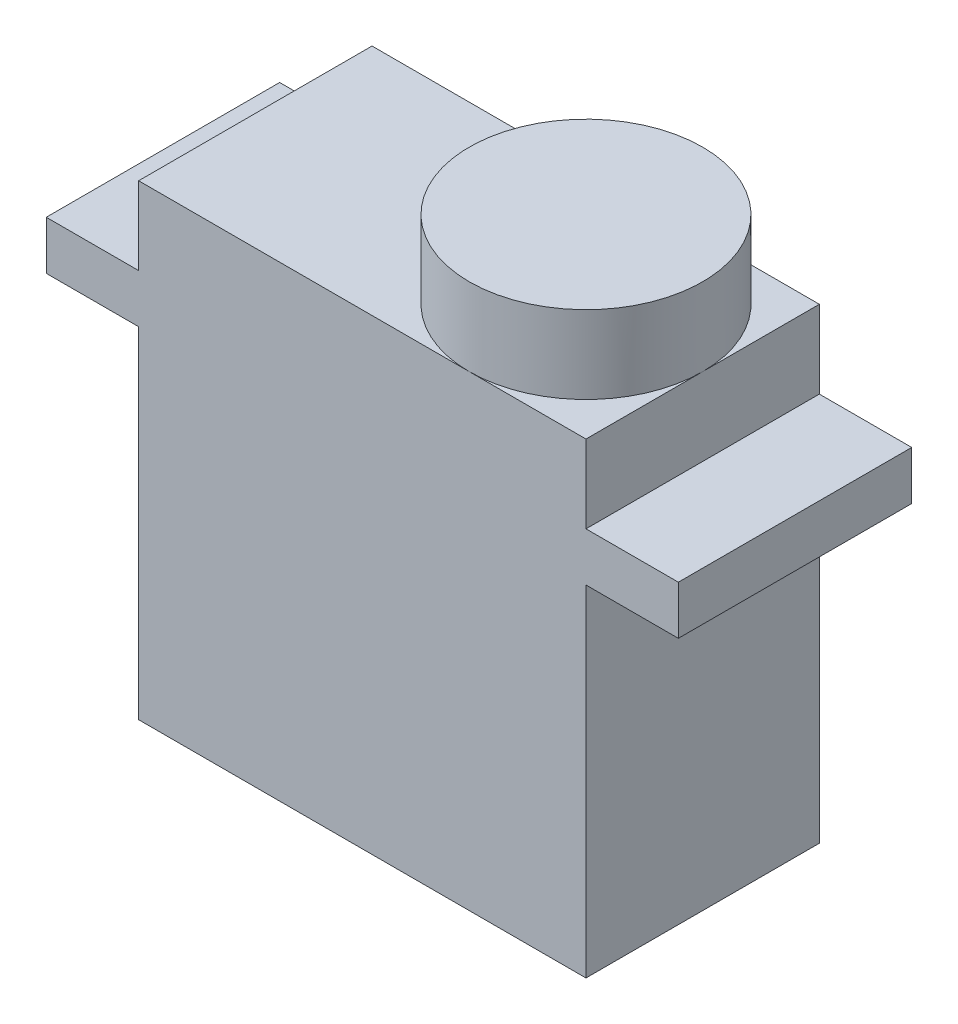
SolidWorks part; units mm, degrees
note: The reader was unsure of these and kept them because the rebuilt part matched: shared geometry of "Sketch1<3>", "Sketch1<4>".
ref_plane "Front Plane" through (0, 0, 0) normal (0, 0, 1) x (1, 0, 0)
ref_plane "Top Plane" through (0, 0, 0) normal (0, 1, 0) x (1, 0, 0)
ref_plane "Right Plane" through (0, 0, 0) normal (1, 0, 0) x (0, 0, -1)
sketch "Sketch1" plane through (0, 0, 0) normal (0, 1, 0) x (1, 0, 0)
  line L1 (-11.5, -6) -> (11.5, -6)
  line L2 (-11.5, -6) -> (-11.5, 6)
  line L3 (-11.5, 6) -> (11.5, 6)
  line L4 (11.5, -6) -> (11.5, 6)
  line L5 (-11.5, -6) -> (11.5, 6) construction
  line L6 (-11.5, 6) -> (11.5, -6) construction
  line L7 (-16.25, -6) -> (16.25, -6)
  line L8 (-16.25, -6) -> (-16.25, 6)
  line L9 (-16.25, 6) -> (16.25, 6)
  line L10 (16.25, -6) -> (16.25, 6)
  line L11 (-16.25, -6) -> (16.25, 6) construction
  line L12 (-16.25, 6) -> (16.25, -6) construction
  circle A0 centre (5.5, 0) radius 6
  point P0 (0, 0)
  point P6 (0, 0)
  dimension "D1" = 23
  dimension "D2" = 12
  dimension "D3" = 32.5
extrude "Boss-Extrude1" add sketch "Sketch1" along normal blind 24 contours A0 L3 L2 L1 | A0 | A0 L4 L9 | A0 L7 L4
extrude "Boss-Extrude2" add sketch "Sketch1<3>" along normal blind 4 from surface at 24 contours A0 starting at face at (0, 24, 0)
sketch "Sketch1<3>" plane through (0, 0, 0) normal (0, 1, 0) x (1, 0, 0) same geometry as "Sketch1"
extrude "Boss-Extrude3" add sketch "Sketch1<4>" against normal blind 2.5 from offset 20 contours L9 L8 L7 L2 | L7 L10 L9 L4
sketch "Sketch1<4>" plane through (0, 0, 0) normal (0, 1, 0) x (1, 0, 0) same geometry as "Sketch1"
